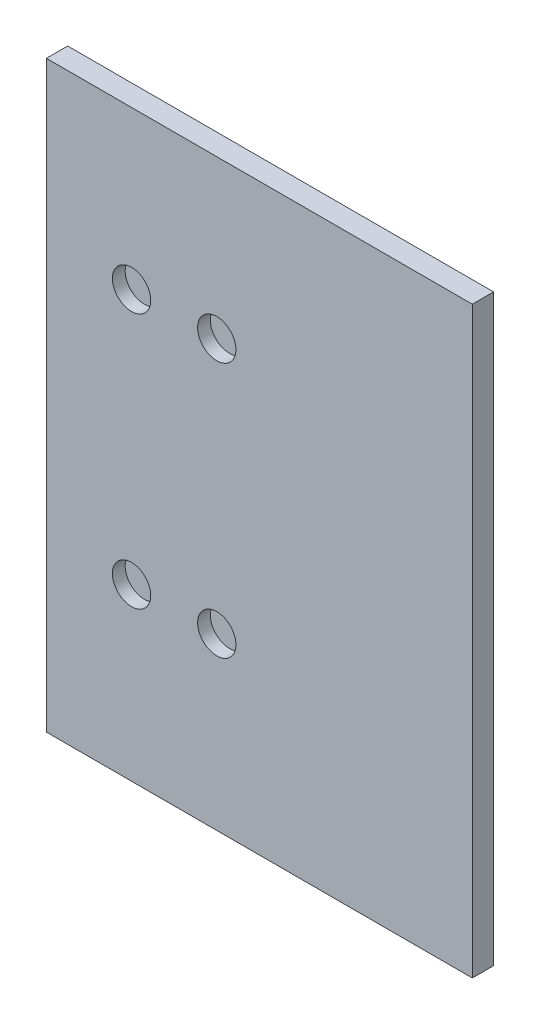
SolidWorks part; units mm, degrees
material "ABS"
ref_plane "Front Plane" through (0, 0, 0) normal (0, 0, 1) x (1, 0, 0)
ref_plane "Top Plane" through (0, 0, 0) normal (0, 1, 0) x (1, 0, 0)
ref_plane "Right Plane" through (0, 0, 0) normal (1, 0, 0) x (0, 0, -1)
sketch "Sketch1" plane through (0, 0, 0) normal (0, 0, 1) x (1, 0, 0)
  line L0 (0, 173.99) -> (63.5, 173.99)
  line L1 (0, 173.99) -> (-63.5, 173.99)
  line L7 (-63.5, 173.99) -> (-63.5, 0)
  line L8 (63.5, 173.99) -> (63.5, 0)
  line L9 (63.5, 0) -> (-63.5, 0)
extrude "Boss-Extrude1" add sketch "Sketch1" along normal blind 6.35
sketch "Sketch2" plane through (0, 0, 0) normal (0, 0, -1) x (-1, 0, 0)
  line L0 (-43.0645, 133.5103) -> (-3.6945, 133.5103)
  line L1 (-43.0645, 51.4703) -> (-3.6945, 51.4703)
  line L2 (-43.0645, 51.4703) -> (-43.0645, 133.5103)
  circle A0 centre (-43.0645, 133.5103) radius 5.715
  circle A1 centre (-3.6945, 133.5103) radius 5.715
  circle A2 centre (-43.0645, 51.4703) radius 5.715
  circle A3 centre (-3.6945, 51.4703) radius 5.715
sketch "Sketch3" plane through (0, 0, 6.35) normal (0, 0, 1) x (1, 0, 0)
  circle A0 centre (-38.1, 127) radius 5.715
  circle A1 centre (-12.7, 127) radius 5.715
  circle A2 centre (-38.1, 50.8) radius 5.715
  circle A3 centre (-12.7, 50.8) radius 5.715
extrude "Cut-Extrude1" cut sketch "Sketch3" against normal blind 3.81 contours A0 | A1 | A3 | A2
extrude "Cut-Extrude2" cut sketch "Sketch2" against normal blind 3.81 contours A0 | A1 | A3 | A2
